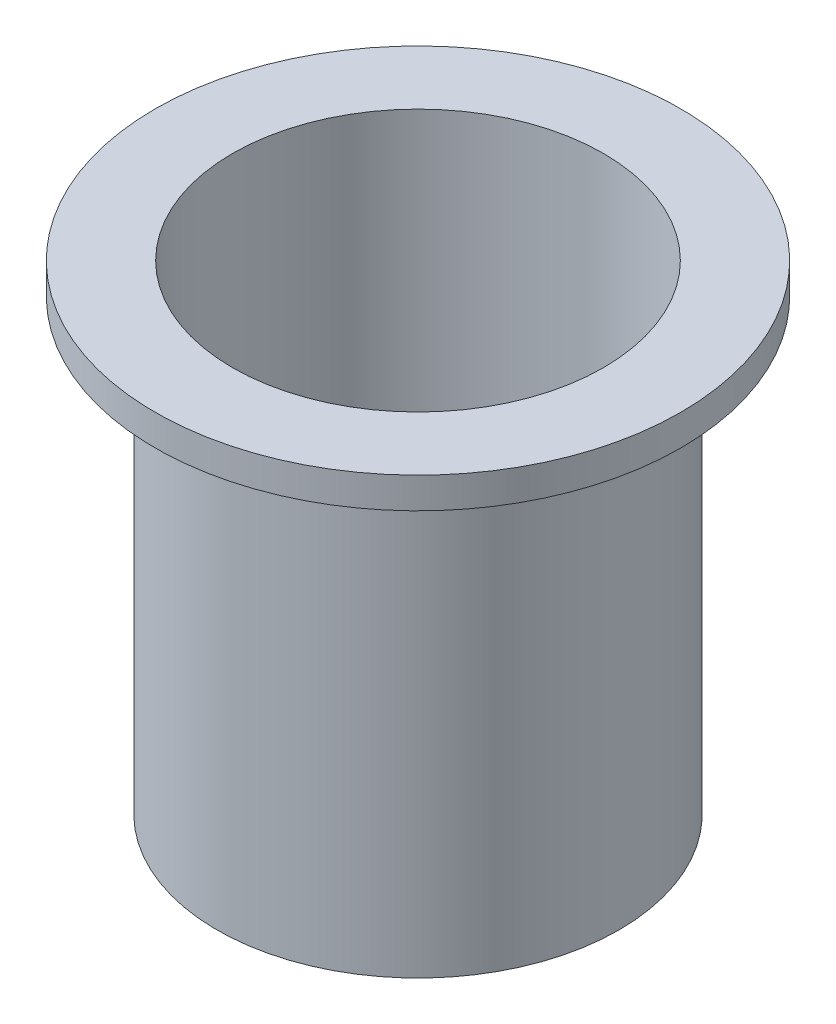
SolidWorks part; units mm, degrees
material "Delrin 2700 NC010, Low Viscosity Acetal Copolymer (SS)"
ref_plane "Front Plane" through (0, 0, 0) normal (0, 0, 1) x (1, 0, 0)
ref_plane "Top Plane" through (0, 0, 0) normal (0, 1, 0) x (1, 0, 0)
ref_plane "Right Plane" through (0, 0, 0) normal (1, 0, 0) x (0, 0, -1)
sketch "Sketch1" plane through (0, 0, 0) normal (0, 0, 1) x (1, 0, 0)
  line L0 (0, -554.3926) -> (0, 27165.2366) construction
  line L1 (41.275, 0) -> (30.744, 0)
  line L2 (41.275, 0) -> (41.275, 92.075)
  line L3 (38.1, 98.425) -> (41.275, 98.425)
  line L9 (38.1, 98.425) -> (38.1, 3.175)
  line L10 (41.275, 98.425) -> (53.975, 98.425)
  line L11 (30.744, 0) -> (0, 0)
  line L12 (41.275, 92.075) -> (53.975, 92.075)
  line L13 (53.975, 98.425) -> (53.975, 92.075)
  line L14 (0, 0) -> (0, 3.175)
  line L15 (0, 3.175) -> (38.1, 3.175)
  dimension "D1" = 76.2
  dimension "D2" = 3.175
  dimension "D4" = 3.175
  dimension "D5" = 88.9
  dimension "D8" = 6.35
  dimension "D9" = 12.7
revolve "Revolve1" add sketch "Sketch1" angle 360 about L0
